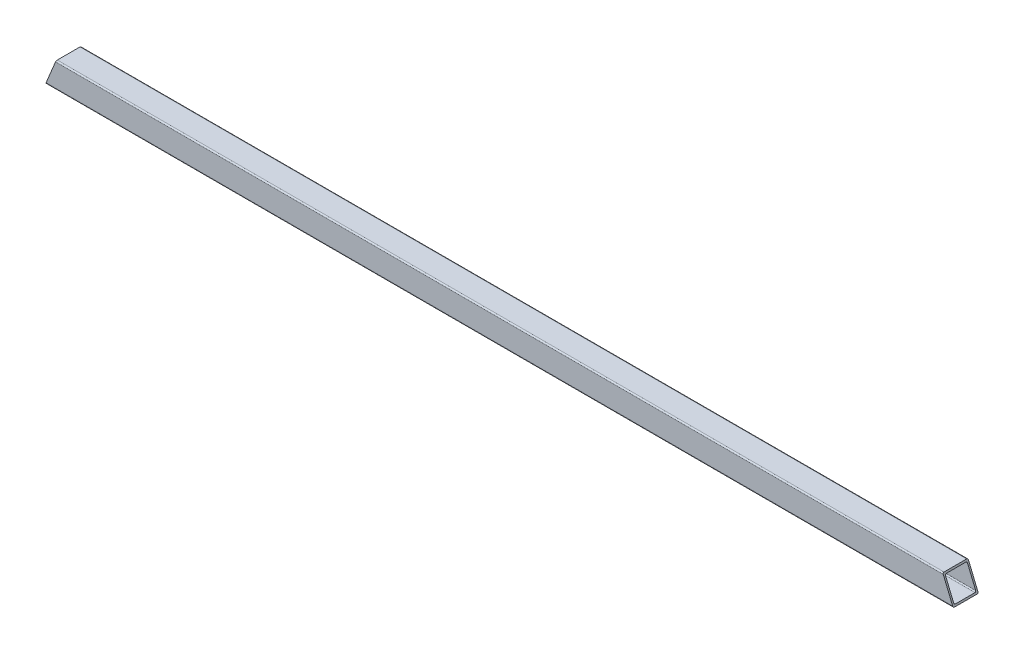
SolidWorks part; units mm, degrees
ref_plane "Front" through (0, 0, 0) normal (0, 0, 1) x (1, 0, 0)
ref_plane "Top" through (0, 0, 0) normal (0, 1, 0) x (1, 0, 0)
ref_plane "Right" through (0, 0, 0) normal (1, 0, 0) x (0, 0, -1)
sketch "Sketch1" plane through (0, 0, 0) normal (1, 0, 0) x (0, 0, -1)
  line L0 (-11.049, 0) -> (-12.7, 0) construction
  line L1 (11.43, -12.7) -> (-11.43, -12.7) construction
  line L2 (12.7, -11.43) -> (12.7, 11.43) construction
  line L3 (11.43, 12.7) -> (-11.43, 12.7) construction
  line L4 (-12.7, -11.43) -> (-12.7, 11.43) construction
  line L5 (12.7, -12.7) -> (-12.7, 12.7) construction
  line L6 (12.7, 12.7) -> (-12.7, -12.7) construction
  line L7 (9.9441, 11.049) -> (-9.9441, 11.049) construction
  line L8 (11.049, 9.9441) -> (11.049, -9.9441) construction
  line L9 (9.9441, -11.049) -> (-9.9441, -11.049) construction
  line L10 (-11.049, 9.9441) -> (-11.049, -9.9441) construction
  line L11 (11.049, 11.049) -> (-11.049, -11.049) construction
  line L12 (11.049, -11.049) -> (-11.049, 11.049) construction
  line L13 (0, -11.049) -> (0, -12.7) construction
  line L14 (11.049, -9.9441) -> (11.049, -12.7) construction
  line L15 (11.049, 0) -> (12.7, 0) construction
  line L16 (11.049, -12.7) -> (12.7, -12.7) construction
  arc A0 (-9.9441, -11.049) -> (-11.049, -9.9441) centre (-9.9441, -9.9441) cw construction
  arc A1 (11.049, -9.9441) -> (9.9441, -11.049) centre (9.9441, -9.9441) cw construction
  arc A2 (9.9441, 11.049) -> (11.049, 9.9441) centre (9.9441, 9.9441) cw construction
  arc A3 (-9.9441, 11.049) -> (-11.049, 9.9441) centre (-9.9441, 9.9441) ccw construction
  arc A4 (11.43, -12.7) -> (12.7, -11.43) centre (11.43, -11.43) ccw construction
  arc A5 (12.7, 11.43) -> (11.43, 12.7) centre (11.43, 11.43) ccw construction
  arc A6 (-11.43, 12.7) -> (-12.7, 11.43) centre (-11.43, 11.43) ccw construction
  arc A7 (-11.43, -12.7) -> (-12.7, -11.43) centre (-11.43, -11.43) cw construction
  point P0 (0, 0)
  point P6 (0, 0)
  dimension "D2" = 1.1049
  dimension "D3" = 1.27
  dimension "Outside Width" = 25.4
  dimension "Ouside Height" = 25.4
  dimension "Inside Height" = 22.098
  dimension "Wall Thickness" = 1.651
sketch "Sketch2" plane through (0, 0, 0) normal (0, 0, 1) x (1, 0, 0)
  line L0 (-457.2, 0) -> (457.2, 0) construction
  point P3 (-433.451, 0)
  point P4 (433.451, 0)
  dimension "Length" = 914.4
  dimension "D1" = 23.749
  dimension "D2" = 23.749
sketch "Sketch4" plane through (0, 0, 0) normal (1, 0, 0) x (0, 0, -1)
  line L8 (12.7, -11.43) -> (12.7, 11.43)
  line L9 (11.43, 12.7) -> (-11.43, 12.7)
  line L10 (-12.7, -11.43) -> (-12.7, 11.43)
  line L11 (11.43, -12.7) -> (-11.43, -12.7)
  line L12 (11.049, 9.9441) -> (11.049, -9.9441)
  line L13 (9.9441, -11.049) -> (-9.9441, -11.049)
  line L14 (-11.049, 9.9441) -> (-11.049, -9.9441)
  line L15 (9.9441, 11.049) -> (-9.9441, 11.049)
  arc A8 (12.7, 11.43) -> (11.43, 12.7) centre (11.43, 11.43) ccw
  arc A9 (-11.43, 12.7) -> (-12.7, 11.43) centre (-11.43, 11.43) ccw
  arc A10 (-12.7, -11.43) -> (-11.43, -12.7) centre (-11.43, -11.43) ccw
  arc A11 (11.43, -12.7) -> (12.7, -11.43) centre (11.43, -11.43) ccw
  arc A12 (9.9441, -11.049) -> (11.049, -9.9441) centre (9.9441, -9.9441) ccw
  arc A13 (-11.049, -9.9441) -> (-9.9441, -11.049) centre (-9.9441, -9.9441) ccw
  arc A14 (-9.9441, 11.049) -> (-11.049, 9.9441) centre (-9.9441, 9.9441) ccw
  arc A15 (11.049, 9.9441) -> (9.9441, 11.049) centre (9.9441, 9.9441) ccw
extrude "Boss-Extrude1" add sketch "Sketch4" along normal up to vertex (-457.2 mm away) and the other way up to vertex (-457.2 mm away) up to point (-457.2, 0, 0) other way up to point (457.2, 0, 0)
sketch "Sketch5" plane through (0, 0, 12.7) normal (0, 0, 1) x (1, 0, 0)
  line L0 (457.2, -12.7) -> (446.679, 12.7)
  line L1 (457.2, 12.7) -> (-457.2, 12.7) construction
  line L2 (446.679, 12.7) -> (457.2, 12.7)
  line L3 (457.2, 12.7) -> (457.2, -12.7)
  dimension "D1" = 22.5
extrude "Cut-Extrude1" cut sketch "Sketch5" against normal through all
mirror "Mirror1" about plane through (0, 0, 0) normal (1, 0, 0) of "Cut-Extrude1"
equation "\"D3@Sketch1\"=\"Outside Width@Sketch1\"*.05"
equation "\"D2@Sketch1\" = \"Inside Height@Sketch1\" * .05"
equation "\"D1@Sketch2\"=\"Outside Width@Sketch1\"-\"Wall Thickness@Sketch1\""
equation "\"D2@Sketch2\"=\"D1@Sketch2\""
equation "\"MidLength\"= 36"
equation "\"Length@Sketch2\"=\"MidLength\""
equation "\"Angle\"=22.5"
equation "\"D1@Sketch5\"=\"Angle\""
